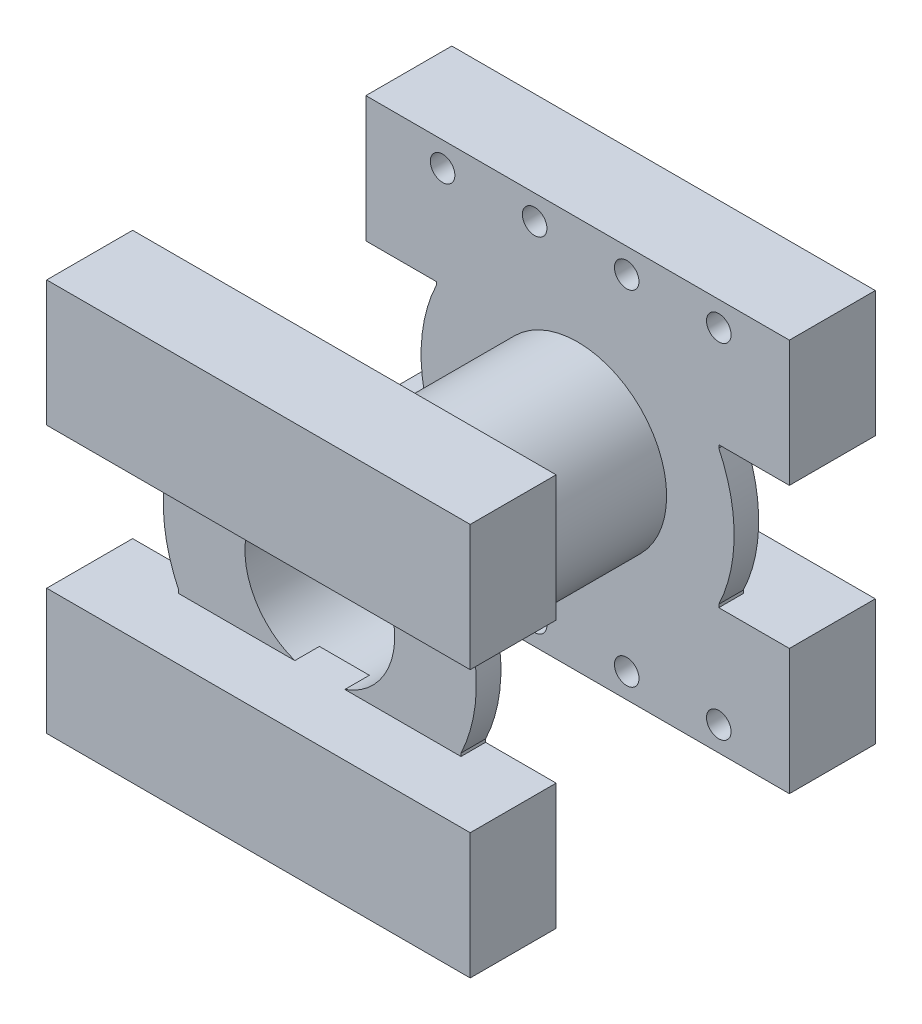
SolidWorks part; units mm, degrees
ref_plane "Front Plane" through (0, 0, 0) normal (0, 0, 1) x (1, 0, 0)
ref_plane "Top Plane" through (0, 0, 0) normal (0, 1, 0) x (1, 0, 0)
ref_plane "Right Plane" through (0, 0, 0) normal (1, 0, 0) x (0, 0, -1)
sketch "Sketch1" plane through (0, 0, 0) normal (0, 0, 1) x (1, 0, 0)
  line L0 (11.5, 5.5057) -> (11.5, 16)
  line L1 (11.5, -16) -> (-11.5, -16)
  line L2 (11.5, -16) -> (11.5, -5.5057)
  line L3 (11.5, 16) -> (-11.5, 16)
  line L4 (-11.5, -16) -> (-11.5, -5.5057)
  line L5 (11.5, -16) -> (-11.5, 16) construction
  line L6 (11.5, 16) -> (-11.5, -16) construction
  line L7 (-11.5, 5.5057) -> (-11.5, 16)
  circle A0 centre (0, 0) radius 6.1
  arc A1 (-11.5, 5.5057) -> (-11.5, -5.5057) centre (0, 0) ccw
  arc A2 (11.5, -5.5057) -> (11.5, 5.5057) centre (0, 0) ccw
  circle A3 centre (0, 0) radius 7.25
  dimension "D1" = 12.2
  dimension "D2" = 25.5
  dimension "D5" = 14.5
  dimension "D3" = 23
  dimension "D4" = 32
extrude "Boss-Extrude1" add sketch "Sketch1" along normal mid plane 2 contours L2 A2 L0 L3 L7 A1 L4 L1 A3 | A3 A0 region at (12.3408, 0, 0) region at (-7.0449, 0, 0)
sketch "Sketch2" plane through (0, 0, 1) normal (0, 0, 1) x (1, 0, 0)
  circle A1 centre (0, 0) radius 6.1
  circle A2 centre (0, 0) radius 7.25
  dimension "D1" = 12.2
  dimension "D2" = 14.5
sketch "Sketch3" plane through (0, 0, -1) normal (0, 0, -1) x (-1, 0, 0)
  line L3 (17.25, 5.75) -> (-17.25, 5.75)
  line L5 (-15.6987, 0) -> (19.4146, 0) construction
  line L6 (17.25, -16) -> (17.25, -5.75)
  line L7 (-17.25, 5.75) -> (-17.25, 16)
  line L8 (-17.25, 16) -> (17.25, 16)
  line L9 (17.25, 16) -> (17.25, 5.75)
  line L10 (-17.25, -16) -> (17.25, -16)
  line L11 (-17.25, -5.75) -> (-17.25, -16)
  line L12 (17.25, -5.75) -> (-17.25, -5.75)
  point P0 (0, 0)
  point P7 (0, 5.75)
  dimension "D1" = 11.5
  dimension "D2" = 34.5
extrude "Boss-Extrude4" add sketch "Sketch2" along normal blind 19
extrude "Boss-Extrude5" add sketch "Sketch3" along normal blind 5 and the other way up to surface (2 mm away) other way up to face at (0, 0, 1)
ref_plane "Plane1" through (0, 0, 10.5) normal (0, 0, 1) x (1, 0, 0)
mirror "Mirror1" about plane through (0, 0, 10.5) normal (0, 0, 1) of "Boss-Extrude5", "Boss-Extrude1"
sketch "Sketch4" plane through (0, 0, -6) normal (0, 0, -1) x (-1, 0, 0)
  line L0 (-17.6861, 0) -> (22.8967, 0) construction
  line L1 (-16.2832, 14) -> (14.9805, 14) construction
  line L2 (0, 20.0666) -> (0, -21.7538) construction
  line L3 (-17.25, 16) -> (-17.25, 5.75) construction
  circle A0 centre (-11.5, 14) radius 1
  circle A8 centre (-4, 14) radius 1
  circle A9 centre (3.5, 14) radius 1
  circle A10 centre (11, 14) radius 1
  circle A11 centre (11, -14) radius 1
  circle A12 centre (3.5, -14) radius 1
  circle A13 centre (-4, -14) radius 1
  circle A14 centre (-11.5, -14) radius 1
  point P17 (11.5, -14)
  dimension "D4" = 2
  dimension "D1" = 14
  dimension "D2" = 4
  dimension "D3" = 5.75
extrude "Cut-Extrude1" cut sketch "Sketch4" against normal blind 10
